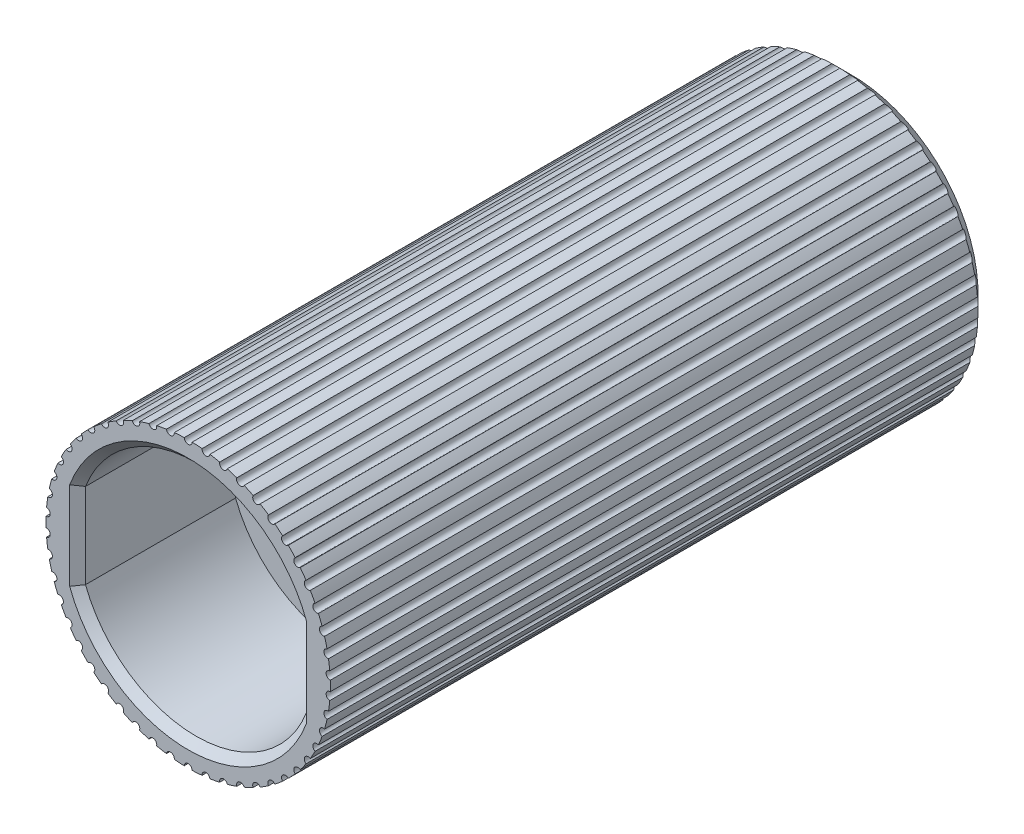
SolidWorks part; units mm, degrees
ref_plane "前视基准面" through (0, 0, 0) normal (0, 0, 1) x (1, 0, 0)
ref_plane "上视基准面" through (0, 0, 0) normal (0, 1, 0) x (1, 0, 0)
ref_plane "右视基准面" through (0, 0, 0) normal (1, 0, 0) x (0, 0, -1)
other "Configuration Table"
sketch "草图2" plane through (0, 0, 40) normal (0, 0, 1) x (1, 0, 0)
  circle A0 centre (0, 0) radius 9
  dimension "D1" = 18
extrude "凸台-拉伸2" add sketch "草图2" along normal blind 40
sketch "草图4" plane through (0, 0, 80) normal (0, 0, 1) x (1, 0, 0)
  line L2 (-7, 2.6926) -> (-7, -2.6926)
  line L4 (7, 2.6926) -> (7, -2.6926)
  arc A0 (-7, -2.6926) -> (7, -2.6926) centre (0, 0) ccw
  arc A1 (7, 2.6926) -> (-7, 2.6926) centre (0, 0) ccw
  dimension "D1" = 15
  dimension "D2" = 14
  dimension "D3" = 7
extrude "切除-拉伸1" cut sketch "草图4" against normal blind 10
sketch "草图6" plane through (0, 0, 40) normal (0, 0, -1) x (-1, 0, 0)
  circle A0 centre (0, 0) radius 9
extrude "凸台-拉伸3" add sketch "草图6" along normal blind 2
chamfer "倒角1" distance 1 angle 45 1 edges at (-9, 0, 38)
sketch "草图7" plane through (0, 0, 80) normal (0, 0, 1) x (1, 0, 0)
  circle A0 centre (0, -9) radius 0.25
  circle A1 centre (0, 0) radius 9 construction
  dimension "D1" = 0.5
extrude "切除-拉伸2" cut sketch "草图7" against normal through all
pattern_circular "阵列(圆周)1" count 50 over 360 about axis through (0, 0, 80) along (0, 0, 1) of "切除-拉伸2"
chamfer "倒角2" distance 0.5 angle 45 4 edges at (0, -7.5, 80) (7, 0, 80) (0, 7.5, 80) (-7, 0, 80)
